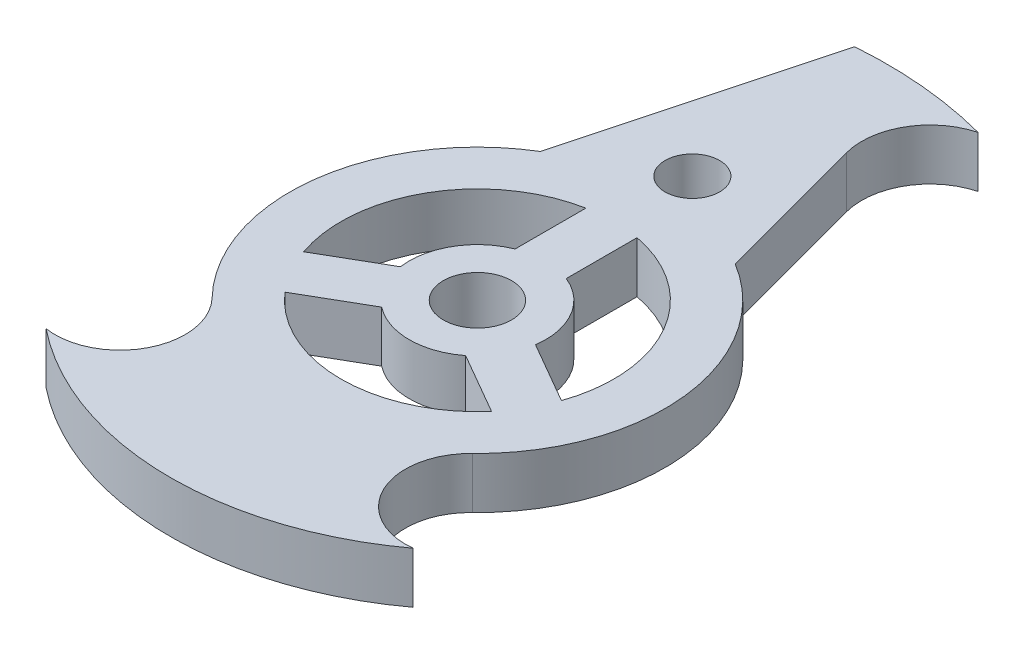
SolidWorks part; units mm, degrees
material "AISI Type A2 Tool Steel"
ref_plane "Front Plane" through (0, 0, 0) normal (0, 0, 1) x (1, 0, 0)
ref_plane "Top Plane" through (0, 0, 0) normal (0, 1, 0) x (1, 0, 0)
ref_plane "Right Plane" through (0, 0, 0) normal (1, 0, 0) x (0, 0, -1)
other "Center of Mass"
other "Bounding Box"
ref_plane "Default Plane" through (-8.9266, -12.7485, 0) normal (-0.1736, 0.9848, 0) x (0.9848, 0.1736, 0)
sketch "Sketch1" plane through (0, 0, 0) normal (0, 1, 0) x (1, 0, 0)
  circle A0 centre (0, 0) radius 6.35
  circle A1 centre (0, 0) radius 34.925
  circle A2 centre (0, 0) radius 76.2 construction
  dimension "D1" = 12.7
  dimension "D2" = 152.4
  dimension "D3" = 69.85
extrude "Boss-Extrude1" add sketch "Sketch1" along normal mid plane 9.525
sketch "Sketch2" plane through (0, 4.7625, 0) normal (0, 1, 0) x (1, 0, 0)
  line L0 (-18.1431, 29.8427) -> (-5.7805, 75.9804)
  line L1 (18.1431, 29.8427) -> (10.5677, 58.1143)
  line L2 (-5.7805, 75.9804) -> (19.5132, 73.6592) construction
  line L3 (0, 0) -> (0, 76.2) construction
  line L4 (0, 0) -> (19.5132, 73.6592) construction
  line L5 (19.5132, 73.6592) -> (-54.0341, 53.7285) construction
  line L6 (-18.1431, 29.8427) -> (0, 29.8427) construction
  line L7 (0, 29.8427) -> (18.1431, 29.8427) construction
  line L8 (-5.7805, 75.9804) -> (0, 97.5536) construction
  line L9 (0, 97.5536) -> (10.5677, 58.1143) construction
  circle A0 centre (0, 0) radius 34.925 construction
  circle A1 centre (0, 0) radius 76.2 construction
  arc A2 (-5.7805, 75.9804) -> (19.5132, 73.6592) centre (0, 0) cw
  arc A3 (10.5677, 58.1143) -> (19.5132, 73.6592) centre (22.835, 61.4013) cw
  arc A4 (18.1431, 29.8427) -> (-18.1431, 29.8427) centre (0, 0) ccw
  circle A5 centre (0, 0) radius 34.925 construction
  dimension "D1" = 60
  dimension "D3" = 12.7
  dimension "D2" = 25.4
  dimension "D4" = 30
extrude "Boss-Extrude2" add sketch "Sketch2" against normal up to surface (9.525 mm away) up to face at (0, -4.7625, 34.925)
sketch "Sketch3" plane through (0, 4.7625, 0) normal (0, 1, 0) x (1, 0, 0)
  line L0 (-35.5767, -44.7261) -> (0, 0) construction
  line L1 (0, 0) -> (33.9941, -45.9404) construction
  line L2 (0, 0) -> (0, -76.2) construction
  line L3 (0, 0) -> (-1.3299, -76.1884) construction
  line L4 (-35.5767, -44.7261) -> (49.9863, -57.5135) construction
  arc A0 (-35.5767, -44.7261) -> (33.9941, -45.9404) centre (0, 0) ccw
  arc A1 (-35.5767, -44.7261) -> (-25.0811, -24.3042) centre (-33.7852, -32.7388) ccw
  circle A2 centre (0, 0) radius 34.925 construction
  arc A3 (33.9941, -45.9404) -> (24.2176, -25.1648) centre (32.6221, -33.8979) cw
  arc A4 (-25.0811, -24.3042) -> (24.2176, -25.1648) centre (0, 0) ccw
  circle A5 centre (0, 0) radius 76.2 construction
  point P6 (-0.9974, -57.1413)
  dimension "D1" = 57.15
  dimension "D2" = 75
  dimension "D3" = 1
  dimension "D4" = 60
extrude "Boss-Extrude3" add sketch "Sketch3" against normal up to surface (9.525 mm away) up to face at (4.237, -4.7625, -41.1164)
sketch "Sketch4" plane through (0, 4.7625, 0) normal (0, 1, 0) x (1, 0, 0)
  line L0 (12.5772, -1.7622) -> (23.9882, -8.3503)
  line L1 (4.7625, 11.7732) -> (4.7625, 24.9495)
  line L2 (0, 0) -> (30.2459, -17.4625) construction
  line L3 (0, 0) -> (0, 34.925) construction
  line L4 (4.7625, 24.9495) -> (0, 24.9495) construction
  line L5 (23.9882, -8.3503) -> (21.6069, -12.4748) construction
  arc A0 (4.7625, 11.7732) -> (12.5772, -1.7622) centre (0, 0) cw
  arc A1 (4.7625, 24.9495) -> (23.9882, -8.3503) centre (0, 0) cw
  circle A2 centre (0, 0) radius 34.925 construction
  dimension "D2" = 9.525
  dimension "D3" = 12.7
  dimension "D1" = 4.7625
  dimension "D4" = 120
extrude "Cut-Extrude1" cut sketch "Sketch4" against normal through all
pattern_circular "CirPattern1" count 3 over 360 about axis through (0, 4.7625, 0) along (0, -1, 0) of "Cut-Extrude1" reverse direction yes
sketch "Sketch5" plane through (0, 4.7625, 0) normal (0, 1, 0) x (1, 0, 0)
  line L0 (0, 0) -> (0, 76.2) construction
  circle A0 centre (0, 40.005) radius 5.08
  arc A1 (18.1431, 29.8427) -> (-18.1431, 29.8427) centre (0, 0) ccw construction
  dimension "D1" = 10.16
extrude "Cut-Extrude2" cut sketch "Sketch5" against normal through all
